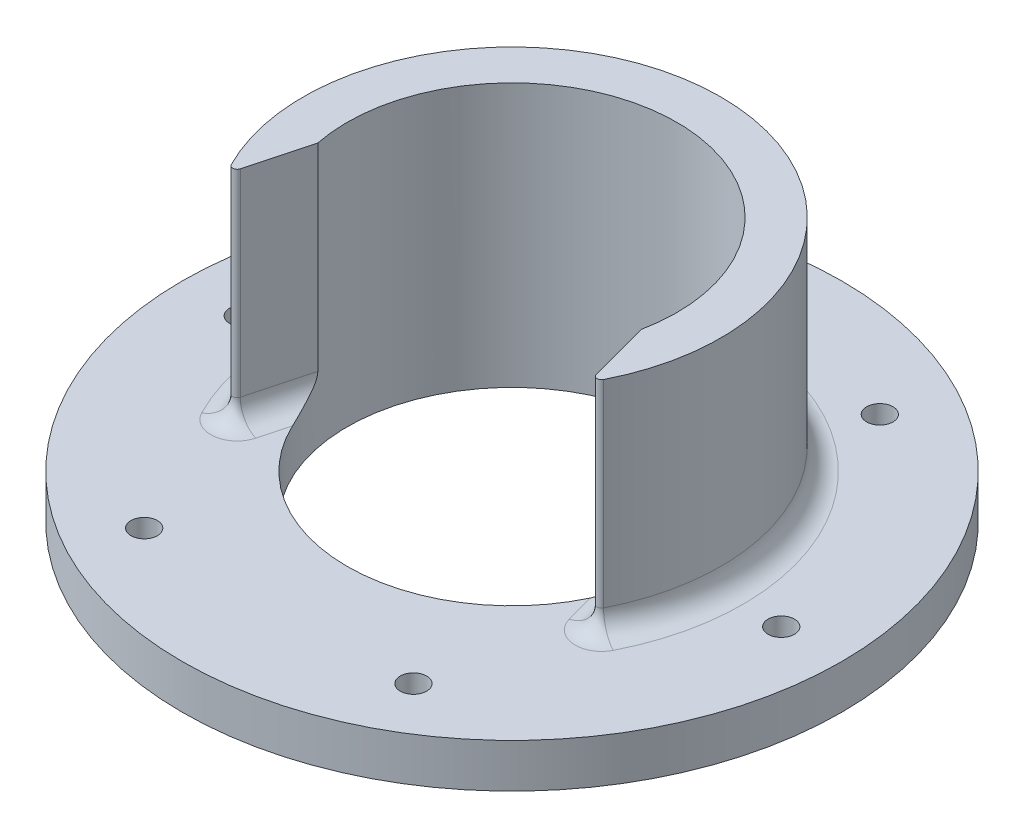
SolidWorks part; units mm, degrees
ref_plane "前基準面" through (0, 0, 0) normal (0, 0, 1) x (1, 0, 0)
ref_plane "上基準面" through (0, 0, 0) normal (0, 1, 0) x (1, 0, 0)
ref_plane "右基準面" through (0, 0, 0) normal (1, 0, 0) x (0, 0, -1)
sketch "草圖2" plane through (0, 0, 0) normal (0, 1, 0) x (1, 0, 0)
  circle A0 centre (0, 0) radius 75
  circle A1 centre (0, 0) radius 37.5
  dimension "D1" = 150
  dimension "D2" = 75
extrude "填料-伸長1" add sketch "草圖2" along normal blind 10
sketch "草圖3" plane through (0, 10, 0) normal (0, 1, 0) x (1, 0, 0)
  line L0 (0, 37.5) -> (0, 0) construction
  line L1 (0, 0) -> (-32.476, -18.75) construction
  line L2 (0, 0) -> (32.476, -18.75) construction
  line L3 (-32.476, -18.75) -> (-41.1362, -23.75)
  line L4 (32.476, -18.75) -> (41.1362, -23.75)
  circle A0 centre (0, 0) radius 37.5 construction
  arc A1 (32.476, -18.75) -> (-32.476, -18.75) centre (0, 0) ccw
  arc A2 (-41.1362, -23.75) -> (41.1362, -23.75) centre (0, 0) cw
  dimension "D1" = 120
  dimension "D2" = 120
  dimension "D3" = 10
  dimension "D4" = 10
extrude "填料-伸長2" add sketch "草圖3" along normal blind 50
chamfer "導角1" distance 10 angle 45 2 edges at (32.476, 35, 18.75) (-32.476, 35, 18.75)
fillet "圓角2" radius 1 2 edges at (41.1362, 35, 23.75) (-41.1362, 35, 23.75)
fillet "圓角3" radius 5 5 edges at (38.6233, 10, 14.3717) (41.349, 10, 22.0634) (-38.6233, 10, 14.3717) (-41.349, 10, 22.0634) (0, 10, -47.5)
sketch "草圖4" plane through (0, 0, 0) normal (0, -1, 0) x (1, 0, 0)
  line L0 (-71.1043, 0) -> (71.1043, 0) construction
  line L5 (0, 67.898) -> (0, -67.7094) construction
  circle A0 centre (-61.25, 0) radius 3
  circle A1 centre (0, 0) radius 37.5 construction
  circle A2 centre (0, 0) radius 37.5 construction
  circle A3 centre (0, 0) radius 75 construction
  circle A4 centre (0, 0) radius 75 construction
  circle A5 centre (0, 0) radius 61.25 construction
  circle A6 centre (-30.625, 53.0441) radius 3
  circle A7 centre (30.625, 53.0441) radius 3
  circle A8 centre (61.25, 0) radius 3
  circle A9 centre (30.625, -53.0441) radius 3
  circle A10 centre (-30.625, -53.0441) radius 3
  point P2 (11.0487, -25.5335)
  point P14 (0, 0)
  point P15 (0, 0)
  point P26 (0, 0)
  point P27 (0, 0)
  point P28 (0, 0)
  point P29 (0, 0)
  point P30 (0, 0)
  point P31 (0, 0)
  point P33 (0, 0)
  dimension "D1" = 6
  dimension "D2" = 13.75
  dimension "D3" = 6
extrude "除料-伸長1" cut sketch "草圖4" against normal through all
